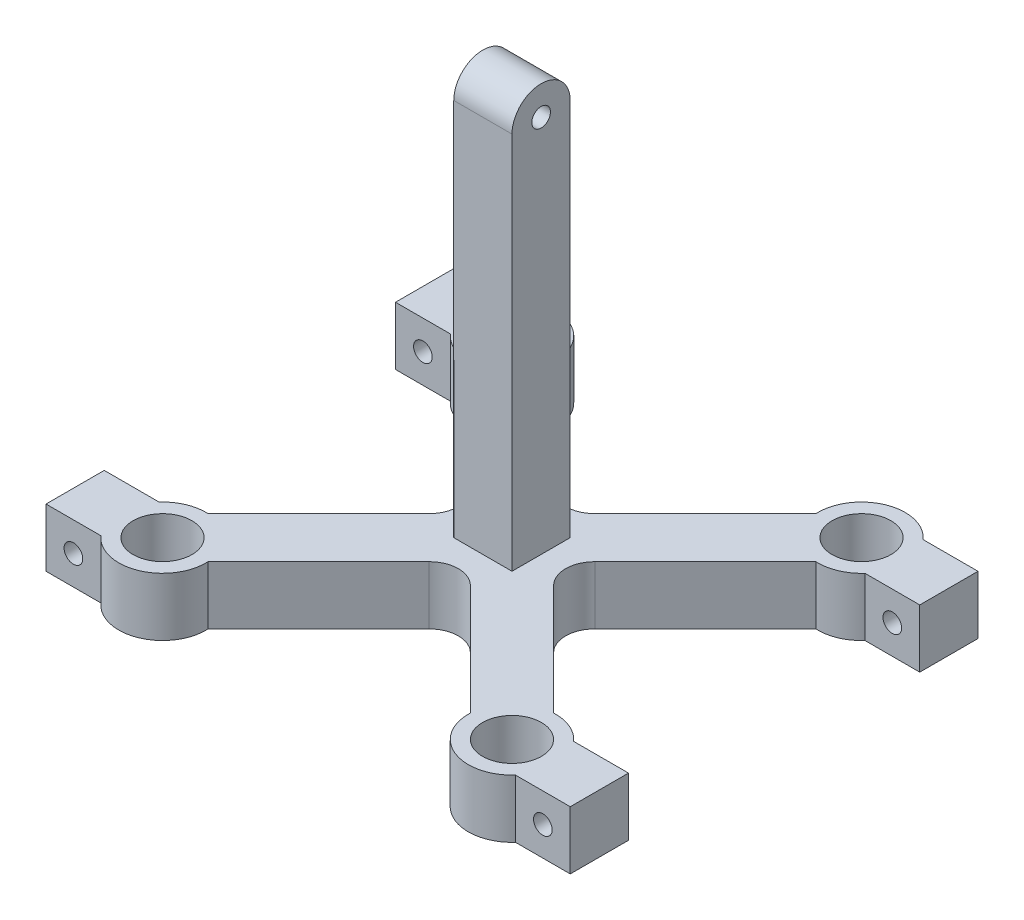
SolidWorks part; units mm, degrees
ref_plane "正面" through (0, 0, 0) normal (0, 0, 1) x (1, 0, 0)
ref_plane "平面" through (0, 0, 0) normal (0, 1, 0) x (1, 0, 0)
ref_plane "右側面" through (0, 0, 0) normal (1, 0, 0) x (0, 0, -1)
sketch "ｽｹｯﾁ1" plane through (0, 0, 0) normal (0, 1, 0) x (1, 0, 0)
  line L0 (0, 0) -> (35355.3391, 35355.3391) construction
  line L1 (-5.5, 0) -> (5.5, 0) construction
  line L2 (3.5355, -10.6773) -> (22.5082, -29.65)
  line L6 (0, 0) -> (35355.3391, -35355.3391) construction
  line L10 (45, -35) -> (35.5902, -35)
  line L29 (35.5902, 25) -> (45, 25)
  line L30 (45, 25) -> (45, 35)
  line L31 (45, 35) -> (35.5902, 35)
  line L32 (3.5355, 10.6773) -> (22.5082, 29.65)
  line L33 (10.6773, 3.5355) -> (29.65, 22.5082)
  line L35 (0, -5.5) -> (0, 5.5) construction
  line L36 (-3.5355, 10.6773) -> (-22.5082, 29.65)
  line L37 (-45, 35) -> (-35.5902, 35)
  line L38 (-45, 25) -> (-45, 35)
  line L39 (-35.5902, 25) -> (-45, 25)
  line L40 (-10.6773, 3.5355) -> (-29.65, 22.5082)
  line L42 (45, -25) -> (45, -35)
  line L43 (35.5902, -25) -> (45, -25)
  line L44 (10.6773, -3.5355) -> (29.65, -22.5082)
  line L47 (-10.6773, -3.5355) -> (-29.65, -22.5082)
  line L48 (-35.5902, -25) -> (-45, -25)
  line L49 (-45, -25) -> (-45, -35)
  line L50 (-45, -35) -> (-35.5902, -35)
  line L51 (-3.5355, -10.6773) -> (-22.5082, -29.65)
  circle A12 centre (30, 30) radius 5.05
  arc A13 (35.5902, 35) -> (22.5082, 29.65) centre (30, 30) ccw
  arc A14 (29.65, 22.5082) -> (35.5902, 25) centre (30, 30) ccw
  circle A15 centre (-30, 30) radius 5.05
  arc A16 (-35.5902, 35) -> (-22.5082, 29.65) centre (-30, 30) cw
  arc A17 (-29.65, 22.5082) -> (-35.5902, 25) centre (-30, 30) cw
  circle A18 centre (30, -30) radius 5.05
  circle A19 centre (-30, -30) radius 5.05
  arc A20 (35.5902, -35) -> (22.5082, -29.65) centre (30, -30) cw
  arc A21 (29.65, -22.5082) -> (35.5902, -25) centre (30, -30) cw
  arc A22 (-29.65, -22.5082) -> (-35.5902, -25) centre (-30, -30) ccw
  arc A23 (-35.5902, -35) -> (-22.5082, -29.65) centre (-30, -30) ccw
  arc A24 (10.6773, 3.5355) -> (10.6773, -3.5355) centre (14.2128, 0) ccw
  arc A25 (-10.6773, -3.5355) -> (-10.6773, 3.5355) centre (-14.2128, 0) ccw
  arc A26 (-3.5355, -10.6773) -> (3.5355, -10.6773) centre (0, -14.2128) cw
  arc A27 (3.5355, 10.6773) -> (-3.5355, 10.6773) centre (0, 14.2128) cw
  dimension "D1" = 45
  dimension "D4" = 10
  dimension "D2" = 10.1
  dimension "D3" = 15
  dimension "D7" = 5
  dimension "D5" = 30
  dimension "D6" = 15
extrude "ﾎﾞｽ - 押し出し1" add sketch "ｽｹｯﾁ1" along normal blind 10
sketch "ｽｹｯﾁ2" plane through (0, 10, 0) normal (0, 1, 0) x (1, 0, 0)
  line L1 (-5, -5) -> (5, -5)
  line L2 (-5, -5) -> (-5, 5)
  line L3 (-5, 5) -> (5, 5)
  line L4 (5, -5) -> (5, 5)
  line L5 (-5, -5) -> (5, 5) construction
  line L6 (-5, 5) -> (5, -5) construction
  point P0 (0, 0)
  dimension "D1" = 10
extrude "ﾎﾞｽ - 押し出し2" add sketch "ｽｹｯﾁ2" along normal blind 70
fillet "ﾌｨﾚｯﾄ3" 2 edges at (0, 80, 5) (0, 80, -5) type full round first side face at (0, 45, 5) second side face at (0, 45, -5) middle face at (0, 80, 0)
sketch "ｽｹｯﾁ3" plane through (5, 0, 0) normal (1, 0, 0) x (0, 0, -1)
  circle A0 centre (0, 75) radius 1.6
  dimension "D1" = 3.2
extrude "ｶｯﾄ - 押し出し1" cut sketch "ｽｹｯﾁ3" against normal through all
sketch "ｽｹｯﾁ4" plane through (0, 0, 35) normal (0, 0, 1) x (1, 0, 0)
  line L0 (-45, 0) -> (-35.5902, 0) construction
  line L1 (-45, 10) -> (-45, 0) construction
  line L2 (45, 10) -> (45, 0) construction
  line L3 (35.5902, 0) -> (45, 0) construction
  circle A0 centre (-40.2951, 5) radius 1.6
  circle A1 centre (40.2951, 5) radius 1.6
  point P7 (-40.2951, 0)
  point P10 (-45, 5)
  point P15 (45, 5)
  point P19 (40.2951, 0)
  dimension "D1" = 3.2
extrude "ｶｯﾄ - 押し出し2" cut sketch "ｽｹｯﾁ4" against normal through all
